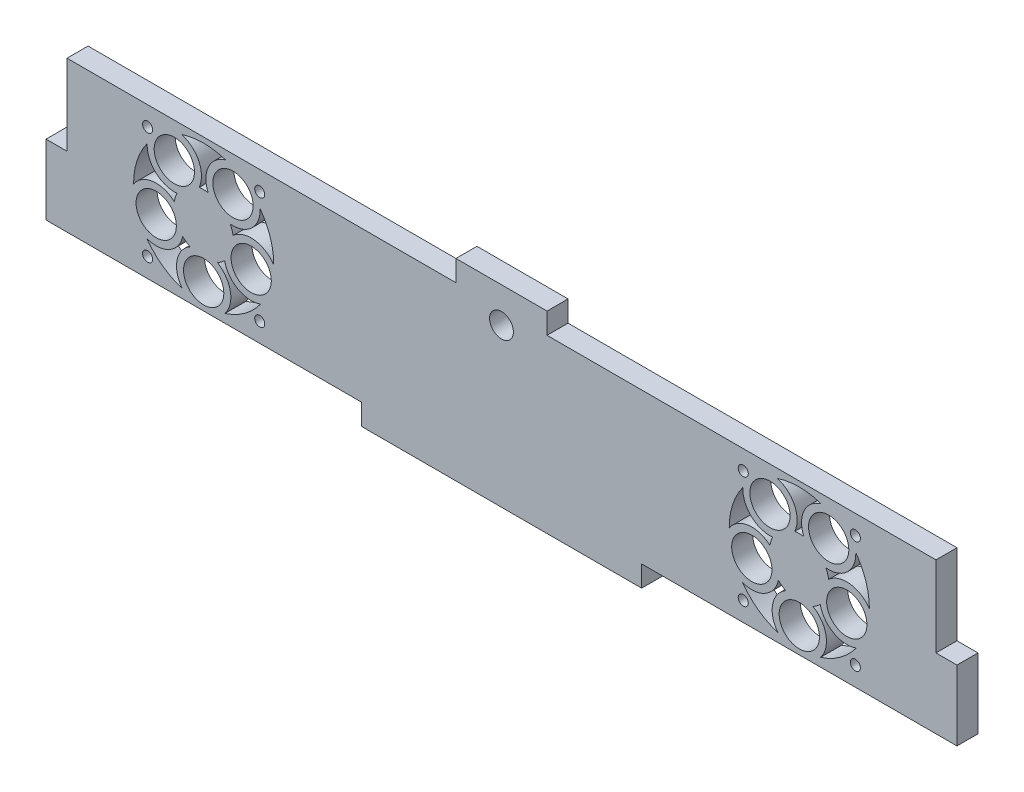
SolidWorks part; units mm, degrees
ref_plane "Front Plane" through (0, 0, 0) normal (0, 0, 1) x (1, 0, 0)
ref_plane "Top Plane" through (0, 0, 0) normal (0, 1, 0) x (1, 0, 0)
ref_plane "Right Plane" through (0, 0, 0) normal (1, 0, 0) x (0, 0, -1)
sketch "Sketch1" plane through (0, 0, 0) normal (0, 0, 1) x (1, 0, 0)
  line L1 (130, 0) -> (-130, 0)
  line L2 (130, 0) -> (130, 49)
  line L3 (130, 49) -> (-130, 49)
  line L4 (-130, 0) -> (-130, 49)
  line L7 (-149.8621, 49) -> (149.8621, 49) construction
extrude "Boss-Extrude1" add sketch "Sketch1" along normal blind 6
sketch "Sketch2" plane through (0, 0, 0) normal (0, 0, -1) x (-1, 0, 0)
  line L0 (-130, 43) -> (-13, 43) construction
  line L1 (-130, 49) -> (-13, 49)
  line L2 (-130, 49) -> (-130, 43)
  line L3 (-130, 43) -> (-13, 43)
  line L4 (-13, 49) -> (-13, 43)
  line L5 (130, 49) -> (13, 49)
  line L6 (130, 49) -> (130, 43)
  line L7 (130, 43) -> (13, 43)
  line L8 (13, 49) -> (13, 43)
  dimension "D1" = 13
  dimension "D2" = 26
extrude "Cut-Extrude1" cut sketch "Sketch2" against normal through all
hole_wizard "M8x1.25 Tapped Hole1" positions "Sketch3" profile "Sketch5" tap size "M8x1.25" standard "ANSI Metric"
sketch "Sketch3" plane through (0, 0, 0) normal (0, 0, -1) x (-1, 0, 0)
  point P2 (0, 39)
sketch "Sketch5" plane through (0, 39, 0) normal (1, 0, 0) x (0, 1, 0)
  line L0 (0, 0) -> (0, 6)
  line L1 (0, 6) -> (3.4, 6)
  line L2 (3.4, 6) -> (3.4, 0)
  line L5 (3.4, 0) -> (0, 0)
  line L11 (0, -6.35) -> (0, 107.95) construction
  dimension "Thread Major Dia." = 6.8
  dimension "Thru Tap Drill Depth" = 6
sketch "Sketch6" plane through (0, 0, 0) normal (0, 0, -1) x (-1, 0, 0)
  line L0 (-124, 20) -> (-130, 20) construction
  line L1 (-130, 43) -> (-124, 43)
  line L2 (-130, 43) -> (-130, 20)
  line L3 (-130, 20) -> (-124, 20)
  line L4 (-124, 43) -> (-124, 20)
  line L5 (-124, 43) -> (-124, 20) construction
  line L7 (124, 20) -> (130, 20)
  line L8 (124, 20) -> (124, 43)
  line L9 (124, 43) -> (130, 43)
  line L10 (130, 20) -> (130, 43)
extrude "Cut-Extrude2" cut sketch "Sketch6" against normal up to next
sketch "Sketch7" plane through (0, 0, 0) normal (0, 0, -1) x (-1, 0, 0)
  line L0 (0, -117.2237) -> (0, 117.2237) construction
  line L1 (-40, 0) -> (40, 0)
  line L2 (-40, 0) -> (-40, -6)
  line L3 (-40, -6) -> (40, -6)
  line L4 (40, 0) -> (40, -6)
  line L5 (130, 0) -> (-130, 0) construction
  line L6 (-130, -6) -> (-40.05, -6) construction
  point P6 (0, 0)
  dimension "D1" = 80
extrude "Boss-Extrude2" add sketch "Sketch7" against normal blind 6
sketch "Sketch8" plane through (0, 0, 0) normal (0, 0, -1) x (-1, 0, 0)
  circle A0 centre (-85, 21.5) radius 20
  circle A1 centre (-85, 21.5) radius 9.5 construction
  circle A2 centre (-85, 21.5) radius 8.5
  dimension "D1" = 40
  dimension "D2" = 17
extrude "Cut-Extrude3" cut sketch "Sketch8" against normal blind 6
sketch "Sketch9" plane through (0, 0, 0) normal (0, 0, -1) x (-1, 0, 0)
  line L0 (-85, 41.5) -> (-85, 1.5) construction
  line L1 (-85, 21.5) -> (-96.7557, 37.6803) construction
  circle A0 centre (-85, 21.5) radius 20 construction
  circle A1 centre (-93.3759, 33.0285) radius 5.75
  circle A2 centre (-85, 21.5) radius 8.5 construction
  arc A3 (-100.7615, 35.3772) -> (-93.3274, 40.7783) centre (-93.3759, 33.0285) ccw
  arc A5 (-93.3274, 40.7783) -> (-100.7615, 35.3772) centre (-85, 21.5) ccw
  dimension "D2" = 2
  dimension "D3" = 1
  dimension "D1" = 36
extrude "Boss-Extrude3" add sketch "Sketch9" against normal blind 6
pattern_circular "CirPattern1" count 5 over 360 of "Boss-Extrude3"
hole_wizard "#6-40 Tapped Hole1" positions "Sketch10" profile "Sketch11" tap size "#6-40" standard "ANSI Inch"
sketch "Sketch10" plane through (0, 0, 0) normal (0, 0, -1) x (-1, 0, 0)
  point P0 (-101, 37.5)
  point P3 (-69, 37.5)
  point P6 (-69, 5.5)
  point P9 (-101, 5.5)
sketch "Sketch11" plane through (101, 37.5, 0) normal (1, 0, 0) x (0, 1, 0)
  line L0 (0, 0) -> (0, 6)
  line L1 (0, 6) -> (1.4351, 6)
  line L2 (1.4351, 6) -> (1.4351, 0)
  line L5 (1.4351, 0) -> (0, 0)
  line L11 (0, -6.35) -> (0, 107.95) construction
  dimension "Thread Major Dia." = 2.8702
  dimension "Thru Tap Drill Depth" = 6
sketch "Sketch12" plane through (0, 0, 0) normal (0, 0, -1) x (-1, 0, 0)
  line L0 (0, 0) -> (0, 39) construction
  circle A0 centre (101, 37.5) radius 1.4351
  circle A1 centre (0, 39) radius 3.4
  circle A2 centre (0, 39) radius 3.4
  circle A3 centre (-93.3759, 33.0285) radius 5.75
  circle A4 centre (-93.3759, 33.0285) radius 5.75
  circle A5 centre (-76.6241, 33.0285) radius 5.75
  circle A6 centre (-76.6241, 33.0285) radius 5.75
  circle A7 centre (-71.4474, 17.0965) radius 5.75
  circle A8 centre (-71.4474, 17.0965) radius 5.75
  circle A9 centre (-85, 7.25) radius 5.75
  arc A10 (-78.722, 40.4891) -> (-83.7156, 29.9024) centre (-76.6241, 33.0285) ccw
  arc A11 (-83.7156, 29.9024) -> (-86.2844, 29.9024) centre (-85, 21.5) ccw
  arc A12 (-86.2844, 29.9024) -> (-91.278, 40.4891) centre (-93.3759, 33.0285) ccw
  arc A13 (-78.722, 40.4891) -> (-91.278, 40.4891) centre (-85, 21.5) ccw
  arc A14 (-78.722, 40.4891) -> (-83.7156, 29.9024) centre (-76.6241, 33.0285) ccw
  arc A15 (-83.7156, 29.9024) -> (-86.2844, 29.9024) centre (-85, 21.5) ccw
  arc A16 (-86.2844, 29.9024) -> (-91.278, 40.4891) centre (-93.3759, 33.0285) ccw
  arc A17 (-78.722, 40.4891) -> (-91.278, 40.4891) centre (-85, 21.5) ccw
  circle A18 centre (-85, 7.25) radius 5.75
  circle A19 centre (-98.5526, 17.0965) radius 5.75
  arc A20 (-65.0003, 21.3972) -> (-68.8803, 33.3387) centre (-85, 21.5) ccw
  arc A21 (-65.0003, 21.3972) -> (-76.6119, 22.875) centre (-71.4474, 17.0965) ccw
  arc A22 (-76.6119, 22.875) -> (-77.4057, 25.318) centre (-85, 21.5) ccw
  arc A23 (-77.4057, 25.318) -> (-68.8803, 33.3387) centre (-76.6241, 33.0285) ccw
  arc A24 (-65.0003, 21.3972) -> (-68.8803, 33.3387) centre (-85, 21.5) ccw
  arc A25 (-65.0003, 21.3972) -> (-76.6119, 22.875) centre (-71.4474, 17.0965) ccw
  arc A26 (-76.6119, 22.875) -> (-77.4057, 25.318) centre (-85, 21.5) ccw
  arc A27 (-77.4057, 25.318) -> (-68.8803, 33.3387) centre (-76.6241, 33.0285) ccw
  circle A28 centre (-98.5526, 17.0965) radius 5.75
  circle A29 centre (-101, 5.5) radius 1.4351
  arc A30 (-78.9175, 2.4474) -> (-68.7595, 9.8276) centre (-85, 21.5) ccw
  arc A31 (-78.9175, 2.4474) -> (-81.1003, 13.9474) centre (-85, 7.25) ccw
  arc A32 (-81.1003, 13.9474) -> (-79.0221, 15.4573) centre (-85, 21.5) ccw
  arc A33 (-79.0221, 15.4573) -> (-68.7595, 9.8276) centre (-71.4474, 17.0965) ccw
  arc A34 (-78.9175, 2.4474) -> (-68.7595, 9.8276) centre (-85, 21.5) ccw
  arc A35 (-78.9175, 2.4474) -> (-81.1003, 13.9474) centre (-85, 7.25) ccw
  arc A36 (-81.1003, 13.9474) -> (-79.0221, 15.4573) centre (-85, 21.5) ccw
  arc A37 (-79.0221, 15.4573) -> (-68.7595, 9.8276) centre (-71.4474, 17.0965) ccw
  arc A38 (-93.3881, 22.875) -> (-104.9997, 21.3972) centre (-98.5526, 17.0965) ccw
  arc A39 (-101.1197, 33.3387) -> (-104.9997, 21.3972) centre (-85, 21.5) ccw
  arc A40 (-101.1197, 33.3387) -> (-92.5943, 25.318) centre (-93.3759, 33.0285) ccw
  arc A41 (-92.5943, 25.318) -> (-93.3881, 22.875) centre (-85, 21.5) ccw
  arc A42 (-93.3881, 22.875) -> (-104.9997, 21.3972) centre (-98.5526, 17.0965) ccw
  arc A43 (-101.1197, 33.3387) -> (-104.9997, 21.3972) centre (-85, 21.5) ccw
  arc A44 (-101.1197, 33.3387) -> (-92.5943, 25.318) centre (-93.3759, 33.0285) ccw
  arc A45 (-92.5943, 25.318) -> (-93.3881, 22.875) centre (-85, 21.5) ccw
  circle A46 centre (-101, 5.5) radius 1.4351
  circle A47 centre (-69, 5.5) radius 1.4351
  arc A48 (-101.2405, 9.8276) -> (-91.0825, 2.4474) centre (-85, 21.5) ccw
  arc A49 (-101.2405, 9.8276) -> (-90.9779, 15.4573) centre (-98.5526, 17.0965) ccw
  arc A50 (-90.9779, 15.4573) -> (-88.8997, 13.9474) centre (-85, 21.5) ccw
  arc A51 (-88.8997, 13.9474) -> (-91.0825, 2.4474) centre (-85, 7.25) ccw
  arc A52 (-101.2405, 9.8276) -> (-91.0825, 2.4474) centre (-85, 21.5) ccw
  arc A53 (-101.2405, 9.8276) -> (-90.9779, 15.4573) centre (-98.5526, 17.0965) ccw
  arc A54 (-90.9779, 15.4573) -> (-88.8997, 13.9474) centre (-85, 21.5) ccw
  arc A55 (-88.8997, 13.9474) -> (-91.0825, 2.4474) centre (-85, 7.25) ccw
  circle A56 centre (-69, 5.5) radius 1.4351
  circle A57 centre (-69, 37.5) radius 1.4351
  circle A58 centre (-69, 37.5) radius 1.4351
  circle A59 centre (-101, 37.5) radius 1.4351
  circle A60 centre (-101, 37.5) radius 1.4351
  circle A61 centre (69, 37.5) radius 1.4351
  circle A62 centre (69, 5.5) radius 1.4351
  arc A63 (88.8997, 13.9474) -> (91.0825, 2.4474) centre (85, 7.25) cw
  arc A64 (90.9779, 15.4573) -> (88.8997, 13.9474) centre (85, 21.5) cw
  arc A65 (101.2405, 9.8276) -> (90.9779, 15.4573) centre (98.5526, 17.0965) cw
  arc A66 (101.2405, 9.8276) -> (91.0825, 2.4474) centre (85, 21.5) cw
  circle A67 centre (101, 5.5) radius 1.4351
  arc A68 (92.5943, 25.318) -> (93.3881, 22.875) centre (85, 21.5) cw
  arc A69 (101.1197, 33.3387) -> (92.5943, 25.318) centre (93.3759, 33.0285) cw
  arc A70 (101.1197, 33.3387) -> (104.9997, 21.3972) centre (85, 21.5) cw
  arc A71 (93.3881, 22.875) -> (104.9997, 21.3972) centre (98.5526, 17.0965) cw
  arc A72 (79.0221, 15.4573) -> (68.7595, 9.8276) centre (71.4474, 17.0965) cw
  arc A73 (81.1003, 13.9474) -> (79.0221, 15.4573) centre (85, 21.5) cw
  arc A74 (78.9175, 2.4474) -> (81.1003, 13.9474) centre (85, 7.25) cw
  arc A75 (78.9175, 2.4474) -> (68.7595, 9.8276) centre (85, 21.5) cw
  circle A76 centre (98.5526, 17.0965) radius 5.75
  arc A77 (77.4057, 25.318) -> (68.8803, 33.3387) centre (76.6241, 33.0285) cw
  arc A78 (76.6119, 22.875) -> (77.4057, 25.318) centre (85, 21.5) cw
  arc A79 (65.0003, 21.3972) -> (76.6119, 22.875) centre (71.4474, 17.0965) cw
  arc A80 (65.0003, 21.3972) -> (68.8803, 33.3387) centre (85, 21.5) cw
  circle A81 centre (85, 7.25) radius 5.75
  arc A82 (78.722, 40.4891) -> (91.278, 40.4891) centre (85, 21.5) cw
  arc A83 (86.2844, 29.9024) -> (91.278, 40.4891) centre (93.3759, 33.0285) cw
  arc A84 (83.7156, 29.9024) -> (86.2844, 29.9024) centre (85, 21.5) cw
  arc A85 (78.722, 40.4891) -> (83.7156, 29.9024) centre (76.6241, 33.0285) cw
  circle A86 centre (71.4474, 17.0965) radius 5.75
  circle A87 centre (76.6241, 33.0285) radius 5.75
  circle A88 centre (93.3759, 33.0285) radius 5.75
  dimension "D2" = 0
  dimension "D3" = 0
  dimension "D4" = 0
  dimension "D5" = 0
  dimension "D6" = 0
  dimension "D7" = 0
  dimension "D8" = 0
  dimension "D9" = 0
  dimension "D10" = 0
  dimension "D11" = 0
  dimension "D12" = 0
  dimension "D13" = 0
  dimension "D14" = 0
  dimension "D15" = 0
  dimension "D16" = 0
extrude "Cut-Extrude4" cut sketch "Sketch12" against normal blind 6
